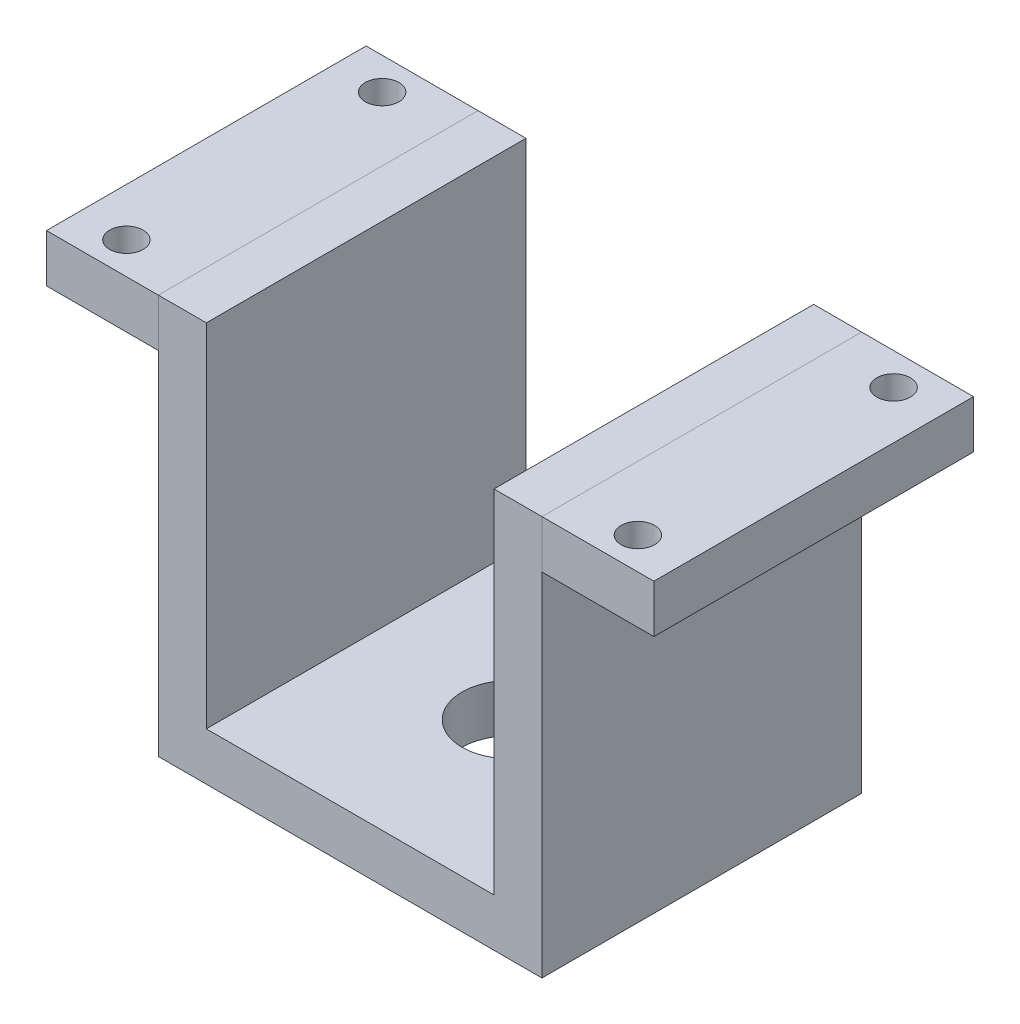
SolidWorks part; units mm, degrees
ref_plane "前基準面" through (0, 0, 0) normal (0, 0, 1) x (1, 0, 0)
ref_plane "上基準面" through (0, 0, 0) normal (0, 1, 0) x (1, 0, 0)
ref_plane "右基準面" through (0, 0, 0) normal (1, 0, 0) x (0, 0, -1)
sketch "草圖1" plane through (0, 0, 0) normal (0, 1, 0) x (1, 0, 0)
  line L0 (0, -131.8131) -> (0, 6458.844) construction
  line L1 (-131.8131, 0) -> (6458.844, 0) construction
  line L3 (-12, -10) -> (12, -10)
  line L4 (-12, -10) -> (-12, 10)
  line L5 (-12, 10) -> (12, 10)
  line L6 (12, -10) -> (12, 10)
  line L7 (-12, -10) -> (12, 10) construction
  line L8 (-12, 10) -> (12, -10) construction
  line L9 (-12, 10) -> (-9, 10)
  line L10 (-12, 10) -> (-12, -10)
  line L11 (-12, -10) -> (-9, -10)
  line L12 (-9, 10) -> (-9, -10)
  line L13 (12, 10) -> (9, 10)
  line L14 (12, 10) -> (12, -10)
  line L15 (12, -10) -> (9, -10)
  line L16 (9, 10) -> (9, -10)
  circle A0 centre (0, 0) radius 3
  point P4 (0, 0)
  dimension "D3" = 6
  dimension "D1" = 24
  dimension "D2" = 20
  dimension "D4" = 3
  dimension "D5" = 3
extrude "填料-伸長2" add sketch "草圖1" along normal blind 3 contours L16 L5 L12 L3 A0 region at (-8.7309, 0, 0)
extrude "填料-伸長3" add sketch "草圖1<3>" along normal blind 25 contours L12 L5 L4 L3 | L5 L16 L3 L6 region at (-10.5, 0, 0) region at (10.5, 0, 0)
sketch "草圖1<3>" plane through (0, 0, 0) normal (0, 1, 0) x (1, 0, 0) same geometry as "草圖1"
sketch "草圖2" plane through (0, 25, 0) normal (0, 1, 0) x (1, 0, 0)
  line L0 (0, -1000) -> (0, 49000) construction
  line L1 (-12, 10) -> (-19, 10)
  line L2 (-12, 10) -> (-12, -10)
  line L3 (-12, -10) -> (-19, -10)
  line L4 (-19, 10) -> (-19, -10)
  line L5 (-12, -10) -> (-9, -10) construction
  line L6 (12, -10) -> (19, -10)
  line L7 (19, 10) -> (19, -10)
  line L8 (12, 10) -> (19, 10)
  line L9 (12, 10) -> (12, -10)
  line L10 (-1000, 0) -> (49000, 0) construction
  circle A0 centre (-16, 8) radius 1.05
  circle A1 centre (16, 8) radius 1.05
  circle A2 centre (16, -8) radius 1.05
  circle A3 centre (-16, -8) radius 1.05
  dimension "D2" = 2.1
  dimension "D1" = 38
  dimension "D3" = 16
  dimension "D4" = 8
extrude "填料-伸長4" add sketch "草圖2" against normal blind 3 separate body
